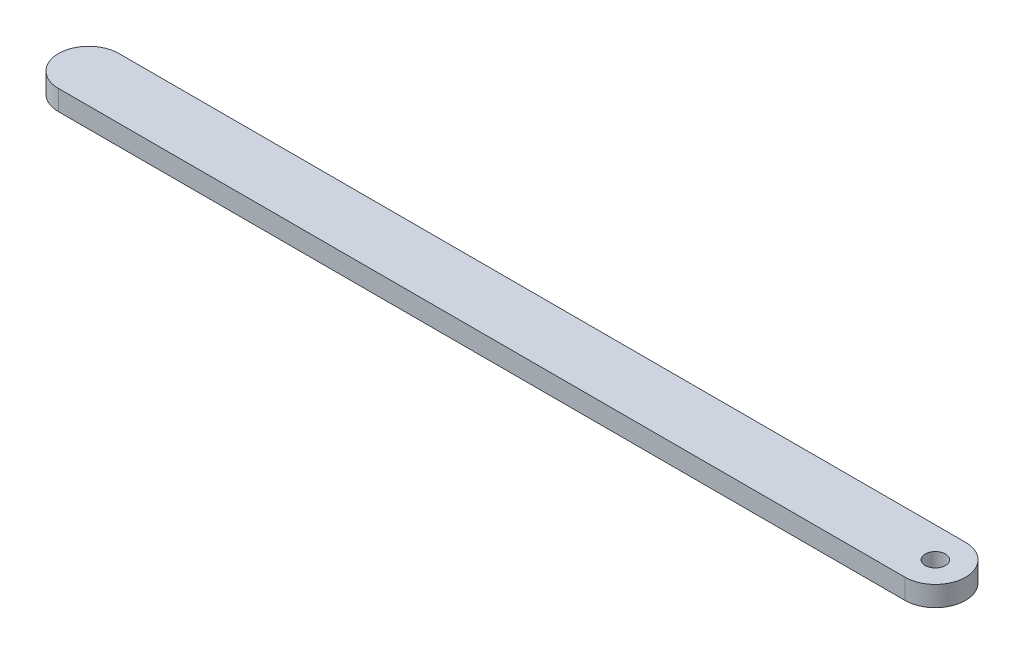
SolidWorks part; units mm, degrees
ref_plane "Front Plane" through (0, 0, 0) normal (0, 0, 1) x (1, 0, 0)
ref_plane "Top Plane" through (0, 0, 0) normal (0, 1, 0) x (1, 0, 0)
ref_plane "Right Plane" through (0, 0, 0) normal (1, 0, 0) x (0, 0, -1)
sketch "Sketch1" plane through (0, 0, 0) normal (0, 1, 0) x (1, 0, 0)
  line L1 (-57.15, -3.81) -> (57.15, -3.81)
  line L2 (-57.15, -3.81) -> (-57.15, 3.81)
  line L3 (-57.15, 3.81) -> (57.15, 3.81)
  line L4 (57.15, -3.81) -> (57.15, 3.81)
  line L5 (-57.15, -3.81) -> (57.15, 3.81) construction
  line L6 (-57.15, 3.81) -> (57.15, -3.81) construction
  point P0 (0, 0)
extrude "Boss-Extrude1" add sketch "Sketch1" along normal blind 2.54
fillet "Fillet1" 2 edges at (57.15, 1.27, 3.81) (57.15, 1.27, -3.81) type full round first side face at (0, 1.27, 3.81) second side face at (0, 1.27, -3.81) middle face at (57.15, 1.27, 0)
fillet "Fillet4" 2 edges at (-57.15, 1.27, -3.81) (-57.15, 1.27, 3.81) type full round first side face at (-1.905, 1.27, -3.81) second side face at (-1.905, 1.27, 3.81) middle face at (-57.15, 1.27, 0)
sketch "Sketch4" plane through (0, 0, 0) normal (0, -1, 0) x (-1, 0, 0)
  circle A1 centre (-53.34, 0) radius 1.27
extrude "Cut-Extrude1" cut sketch "Sketch4" against normal blind 2.54
sketch "Sketch6" plane through (0, 0, 0) normal (0, -1, 0) x (-1, 0, 0)
  circle A0 centre (53.2345, 0) radius 0.762
extrude "Boss-Extrude3" add sketch "Sketch6" along normal blind 2.54
